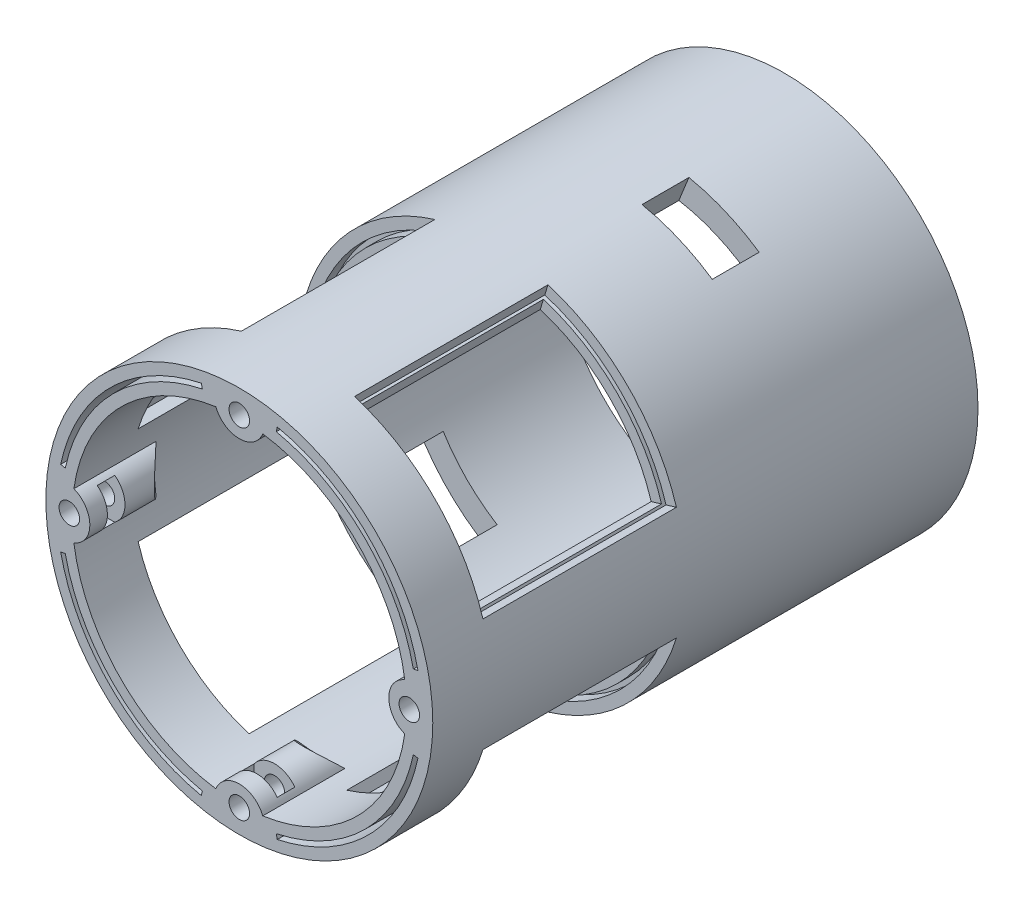
SolidWorks part; units mm, degrees
material "PEI"
ref_plane "Alzado" through (0, 0, 0) normal (0, 0, 1) x (1, 0, 0)
ref_plane "Planta" through (0, 0, 0) normal (0, 1, 0) x (1, 0, 0)
ref_plane "Vista lateral" through (0, 0, 0) normal (1, 0, 0) x (0, 0, -1)
sketch "Croquis1" plane through (0, 0, 0) normal (0, 0, 1) x (1, 0, 0)
  circle A0 centre (0, 0) radius 33
  circle A1 centre (0, 0) radius 28.5
  dimension "D1" = 66
  dimension "D2" = 4.5
extrude "Boss-Extrude1" add sketch "Croquis1" along normal blind 93
sketch "Croquis2" plane through (0, 0, 93) normal (0, 0, 1) x (1, 0, 0)
  line L0 (0, 0) -> (-6.4764, -30.4693) construction
  line L1 (0, 0) -> (-30.4693, -6.4764) construction
  line L2 (0, 0) -> (0, -30.5) construction
  line L3 (0, 0) -> (-30.5, 0) construction
  line L4 (-30.4693, -6.4764) -> (-29.6868, -6.3101)
  line L5 (-6.4764, -30.4693) -> (-6.3101, -29.6868)
  line L6 (-30.4693, 6.4764) -> (-29.6868, 6.3101)
  line L7 (-6.4764, 30.4693) -> (-6.3101, 29.6868)
  line L8 (6.4764, 30.4693) -> (6.3101, 29.6868)
  line L9 (30.4693, 6.4764) -> (29.6868, 6.3101)
  line L10 (30.4693, -6.4764) -> (29.6868, -6.3101)
  line L11 (6.4764, -30.4693) -> (6.3101, -29.6868)
  circle A0 centre (0, 0) radius 30.35 construction
  circle A1 centre (0, 0) radius 31.15 construction
  circle A2 centre (0, 0) radius 33 construction
  circle A3 centre (0, 0) radius 30.75 construction
  arc A4 (-6.4764, -30.4693) -> (-30.4693, -6.4764) centre (0, 0) cw
  arc A5 (-6.3101, -29.6868) -> (-29.6868, -6.3101) centre (0, 0) cw
  arc A6 (-30.4693, 6.4764) -> (-6.4764, 30.4693) centre (0, 0) cw
  arc A7 (-29.6868, 6.3101) -> (-6.3101, 29.6868) centre (0, 0) cw
  arc A8 (6.4764, 30.4693) -> (30.4693, 6.4764) centre (0, 0) cw
  arc A9 (6.3101, 29.6868) -> (29.6868, 6.3101) centre (0, 0) cw
  arc A10 (30.4693, -6.4764) -> (6.4764, -30.4693) centre (0, 0) cw
  arc A11 (29.6868, -6.3101) -> (6.3101, -29.6868) centre (0, 0) cw
  circle A12 centre (0, 0) radius 28.5 construction
  point P4 (-6.3933, -30.078)
  point P32 (0, 0)
  dimension "D3" = 12
  dimension "D4" = 12
  dimension "D1" = 0.8
  dimension "D2" = 4.5
  dimension "D6" = 2.25
  dimension "D5" = 4
extrude "Cortar-Extruir1" cut sketch "Croquis2" against normal blind 45
ref_axis "Eje1" through (0, 0, 93) along (0, 0, -1)
ref_plane "Plano2" through (0, 0, 0) normal (0.9563, -0.2924, 0) x (0, 0, -1)
sketch "Croquis4" plane through (0, 0, 0) normal (0.9563, -0.2924, 0) x (0, 0, -1)
  line L0 (-83, 33) -> (-83, 28.266)
  line L1 (0, 33) -> (-93, 33) construction
  line L2 (-83, 28.266) -> (-50, 28.266)
  line L4 (-50, 33) -> (-83, 33)
  line L5 (-97, 29) -> (-42, 29) construction
  line L6 (-93, 33) -> (-93, -33) construction
  line L14 (-50, 28.266) -> (-50, 33)
  dimension "D1" = 4.734
  dimension "D6" = 10
revolve "Cortar-Revolución2" cut sketch "Croquis4" angle 56 about axis through (0, 0, 93) along (0, 0, -1)
pattern_circular "MatrizC2" count 4 over 360 about axis through (0, 0, 93) along (0, 0, -1) of "Cortar-Revolución2"
sketch "Sketch8" plane through (0, 0, 0) normal (0, 0, -1) x (-1, 0, 0)
  arc A0 (-4, -28.2179) -> (4, -28.2179) centre (0, 0) ccw
  circle A1 centre (0, 0) radius 28.5 construction
  arc A2 (-4, -28.2179) -> (4, -28.2179) centre (0, -29.7959) cw
  arc A3 (-28.2179, 4) -> (-28.2179, -4) centre (0, 0) ccw
  arc A4 (-28.2179, 4) -> (-28.2179, -4) centre (-29.7959, 0) cw
  arc A5 (4, 28.2179) -> (-4, 28.2179) centre (0, 0) ccw
  arc A6 (4, 28.2179) -> (-4, 28.2179) centre (0, 29.7959) cw
  arc A7 (28.2179, -4) -> (28.2179, 4) centre (0, 0) ccw
  arc A8 (28.2179, -4) -> (28.2179, 4) centre (29.7959, 0) cw
  point P8 (0, -25.4959)
  point P20 (0, 0)
  dimension "D1" = 4.3
  dimension "D2" = 8
  dimension "D3" = 4
extrude "Boss-Extrude4" add sketch "Sketch8" against normal blind 11
sketch "Sketch9" plane through (0, 0, 0) normal (0, 0, -1) x (-1, 0, 0)
  circle A0 centre (0, -29) radius 1.75
  circle A1 centre (0, 0) radius 29 construction
  circle A2 centre (0, 0) radius 33 construction
  circle A3 centre (-29, 0) radius 1.75
  circle A4 centre (0, 29) radius 1.75
  circle A5 centre (29, 0) radius 1.75
  point P16 (0, 0)
  dimension "D1" = 4
  dimension "D2" = 3.5
  dimension "D3" = 4
extrude "Cut-Extrude3" cut sketch "Sketch9" against normal blind 10
ref_plane "Mid plane" through (0, 0, 46.5) normal (0, 0, 1) x (1, 0, 0)
mirror "Mirror1" about plane through (0, 0, 46.5) normal (0, 0, 1) of "Cut-Extrude3", "Boss-Extrude4"
ref_plane "Plano para USB y Switch" through (-23.3345, -23.3345, 0) normal (-0.7071, -0.7071, 0) x (0, 0, -1)
sketch "Sketch10" plane through (-23.3345, -23.3345, 0) normal (-0.7071, -0.7071, 0) x (0, 0, -1)
  line L0 (0, -33) -> (0, 33) construction
  line L1 (-10.5, 7.5) -> (-3.5, 7.5)
  line L2 (-10.5, 7.5) -> (-10.5, -7.5)
  line L3 (-10.5, -7.5) -> (-3.5, -7.5)
  line L4 (-3.5, 7.5) -> (-3.5, -7.5)
  line L5 (-10.5, 7.5) -> (-3.5, -7.5) construction
  line L6 (-10.5, -7.5) -> (-3.5, 7.5) construction
  line L8 (-42, 6.5) -> (-34, 6.5)
  line L9 (-42, 6.5) -> (-42, -6.5)
  line L10 (-42, -6.5) -> (-34, -6.5)
  line L11 (-34, 6.5) -> (-34, -6.5)
  line L12 (-42, 6.5) -> (-34, -6.5) construction
  line L13 (-42, -6.5) -> (-34, 6.5) construction
  point P0 (-7, 0)
  point P9 (-38, 0)
  dimension "D1" = 7
  dimension "D2" = 15
  dimension "D3" = 7
  dimension "D4" = 13
  dimension "D5" = 8
  dimension "D6" = 38
extrude "Corte USB y Switch" cut sketch "Sketch10" against normal blind 10
ref_plane "Plano USB PCB_C" through (12.362, 30.5971, 0) normal (0.3746, 0.9272, 0) x (0, 0, -1)
sketch "Sketch11" plane through (12.362, 30.5971, 0) normal (0.3746, 0.9272, 0) x (0, 0, -1)
  line L0 (0, -33) -> (0, 33) construction
  line L1 (-30.9, 6) -> (-22.9, 6)
  line L2 (-30.9, 6) -> (-30.9, -7)
  line L3 (-30.9, -7) -> (-22.9, -7)
  line L4 (-22.9, 6) -> (-22.9, -7)
  line L5 (-30.9, 6) -> (-22.9, -7) construction
  line L6 (-30.9, -7) -> (-22.9, 6) construction
  point P0 (-26.9, -0.5)
  dimension "D1" = 0.5
  dimension "D2" = 8
  dimension "D3" = 13
  dimension "D4" = 22.9
extrude "Cut-Extrude5" cut sketch "Sketch11" against normal blind 10
chamfer "Chamfer1" distance 3 angle 45 4 edges at (0, 28.5, 82) (-28.5, 0, 82) (28.5, 0, 82) (0, -28.5, 82)
ref_plane "Plano3" through (0, 0, 90) normal (0, 0, 1) x (1, 0, 0)
sketch "Croquis6" plane through (0, 0, 90) normal (0, 0, 1) x (1, 0, 0)
  line L0 (-3.4641, -29) -> (-3.4641, -27.2483)
  line L1 (-29, -3.4641) -> (-27.2483, -3.4641)
  line L2 (-29, -3.4641) -> (-26, -1.7321) construction
  line L3 (-26, -1.7321) -> (-26, 1.7321) construction
  line L4 (-3.4641, -29) -> (-1.7321, -32)
  line L5 (-1.7321, -32) -> (1.7321, -32)
  line L6 (1.7321, -32) -> (3.4641, -29)
  line L7 (3.4641, -29) -> (3.4641, -27.2483)
  line L8 (-26, 1.7321) -> (-29, 3.4641) construction
  line L9 (2.5981, -27.5) -> (1.7321, -26) [skipped]
  line L10 (-1.7321, -26) -> (-2.5981, -27.5) [skipped]
  line L11 (0, -26) -> (-1.7321, -26) [skipped]
  line L12 (-29, 3.4641) -> (-32, 1.7321)
  line L13 (-32, 1.7321) -> (-32, -1.7321)
  line L14 (-32, -1.7321) -> (-29, -3.4641)
  line L15 (-29, 3.4641) -> (-27.2483, 3.4641)
  line L16 (-3.4641, 29) -> (-3.4641, 27.2483)
  line L17 (1.7321, -32) -> (3.4641, -29)
  line L18 (3.4641, -29) -> (1.7321, -26) construction
  line L19 (1.7321, -26) -> (-1.7321, -26) construction
  line L20 (-1.7321, -26) -> (-3.4641, -29) construction
  line L21 (-3.4641, -29) -> (-1.7321, -32)
  line L22 (-1.7321, -32) -> (1.7321, -32)
  line L23 (3.4641, 29) -> (1.7321, 32)
  line L24 (1.7321, 32) -> (-1.7321, 32)
  line L25 (-1.7321, 32) -> (-3.4641, 29)
  line L26 (-3.4641, 29) -> (-1.7321, 26) construction
  line L27 (-1.7321, 26) -> (1.7321, 26) construction
  line L28 (1.7321, 26) -> (3.4641, 29) construction
  line L29 (3.4641, 29) -> (3.4641, 27.2483)
  line L30 (29, 3.4641) -> (27.2483, 3.4641)
  line L31 (29, 3.4641) -> (26, 1.7321) construction
  line L32 (26, 1.7321) -> (26, -1.7321) construction
  line L33 (26, -1.7321) -> (29, -3.4641) construction
  line L34 (29, -3.4641) -> (32, -1.7321)
  line L35 (32, -1.7321) -> (32, 1.7321)
  line L36 (32, 1.7321) -> (29, 3.4641)
  line L37 (29, -3.4641) -> (27.2483, -3.4641)
  circle A0 centre (0, -29) radius 3 construction
  arc A1 (4, -28.2179) -> (-4, -28.2179) centre (0, -29.7959) ccw construction
  arc A2 (3.4641, -27.2483) -> (-3.4641, -27.2483) centre (0, -29.7959) ccw
  circle A3 centre (-29, 0) radius 3 construction
  arc A4 (-28.2179, -4) -> (-28.2179, 4) centre (-29.7959, 0) ccw construction
  arc A5 (-27.2483, -3.4641) -> (-27.2483, 3.4641) centre (-29.7959, 0) ccw
  circle A6 centre (0, -29) radius 3 construction
  circle A7 centre (0, 29) radius 3 construction
  arc A8 (-4, 28.2179) -> (4, 28.2179) centre (0, 29.7959) ccw construction
  arc A9 (-3.4641, 27.2483) -> (3.4641, 27.2483) centre (0, 29.7959) ccw
  circle A10 centre (29, 0) radius 3 construction
  arc A11 (28.2179, 4) -> (28.2179, -4) centre (29.7959, 0) ccw construction
  arc A12 (27.2483, 3.4641) -> (27.2483, -3.4641) centre (29.7959, 0) ccw
  dimension "D1" = 6
  dimension "D2" = 6
  dimension "D3" = 6
  dimension "D4" = 6
extrude "Cortar-Extruir2" cut sketch "Croquis6" against normal blind 3 contours L7 A2 L0 L4 L5 L6 | L1 A5 L15 L12 L13 L14 | L30 A12 L37 L34 L35 L36 | L16 A9 L29 L23 L24 L25 region at (0, -28.7019, 90) region at (-28.7019, 0, 90) region at (0, 28.7019, 90) region at (28.7019, 0, 90)
mirror "Simetría1" about plane through (0, 0, 46.5) normal (0, 0, 1) of "Cortar-Extruir2"
equation "\"D6@Croquis2\"=\"D2@Croquis2\"/2"
